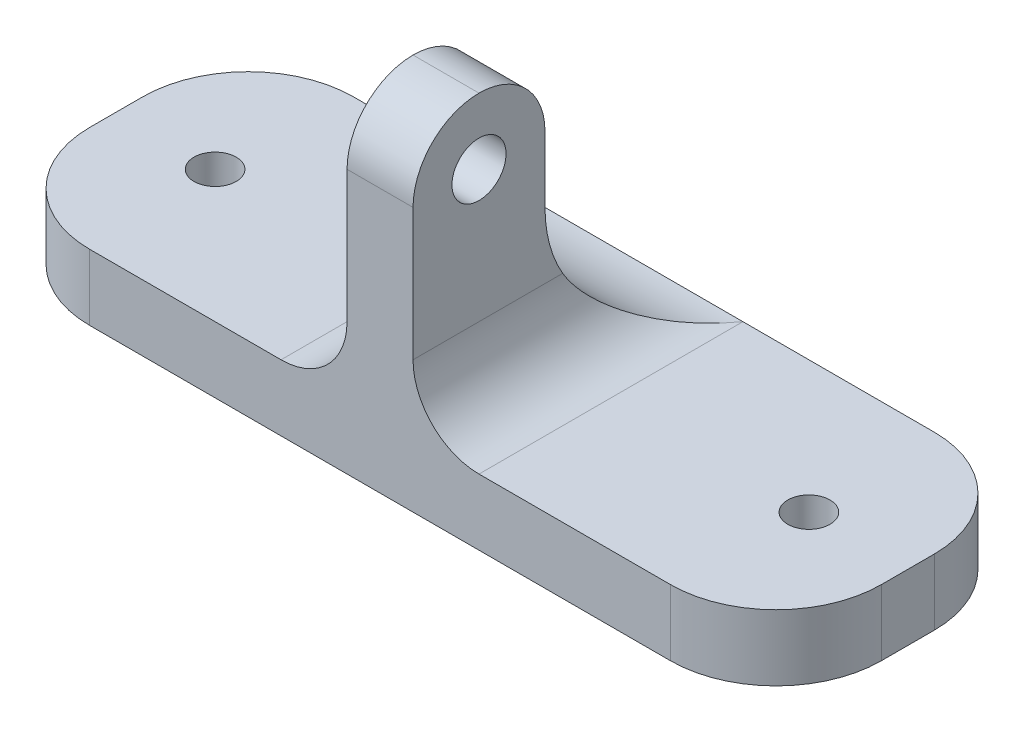
SolidWorks part; units mm, degrees
ref_plane "前视基准面" through (0, 0, 0) normal (0, 0, 1) x (1, 0, 0)
ref_plane "上视基准面" through (0, 0, 0) normal (0, 1, 0) x (1, 0, 0)
ref_plane "右视基准面" through (0, 0, 0) normal (1, 0, 0) x (0, 0, -1)
sketch "草图1" plane through (0, 0, 0) normal (0, 0, 1) x (1, 0, 0)
  line L1 (0, 0) -> (20, 0)
  line L2 (0, 0) -> (0, 15)
  line L3 (0, 15) -> (20, 15)
  line L4 (20, 0) -> (20, 15)
  dimension "D1" = 20
  dimension "D2" = 15
extrude "凸台-拉伸1" add sketch "草图1" along normal blind 10
sketch "草图2" plane through (0, 0, 0) normal (0, -1, 0) x (1, 0, 0)
  line L0 (20, 10) -> (20, 0) construction
  line L1 (-20, 10) -> (40, 10)
  line L2 (-20, 10) -> (-20, -10)
  line L3 (-20, -10) -> (40, -10)
  line L4 (40, 10) -> (40, -10)
  line L5 (0, 10) -> (20, 10) construction
  dimension "D1" = 60
  dimension "D2" = 20
  dimension "D3" = 20
  dimension "D4" = 0
extrude "凸台-拉伸2" add sketch "草图2" against normal blind 5
sketch "草图3" plane through (0, 0, 0) normal (0, -1, 0) x (1, 0, 0)
  line L0 (-20, 10) -> (40, 10) construction
  line L1 (-20, 10) -> (-20, -10) construction
  circle A0 centre (-12.5, 0) radius 1.6
  circle A1 centre (32.5, 0) radius 1.6
  dimension "D1" = 3.2
  dimension "D2" = 3.2
  dimension "D3" = 10
  dimension "D4" = 10
  dimension "D5" = 45
  dimension "D6" = 7.5
extrude "切除-拉伸1" cut sketch "草图3" against normal blind 21
fillet "圆角1" radius 8 4 edges at (-20, 2.5, -10) (-20, 2.5, 10) (40, 2.5, -10) (40, 2.5, 10)
sketch "草图4" plane through (0, 0, 10) normal (0, 0, 1) x (1, 0, 0)
  line L0 (-12, 0) -> (32, 0) construction
  line L1 (20, 5) -> (20, 15) construction
  circle A0 centre (10, 8) radius 2.1
  dimension "D1" = 4.2
  dimension "D2" = 8
  dimension "D3" = 10
extrude "切除-拉伸2" [suppressed] cut sketch "草图4" against normal blind 21
sketch "草图5" plane through (0, 0, 10) normal (0, 0, 1) x (1, 0, 0)
  line L0 (0, 5) -> (-12, 5) construction
  line L1 (-0.15, 5) -> (-10.15, 5)
  line L2 (-0.15, 5) -> (-0.15, 0)
  line L3 (-0.15, 0) -> (-10.15, 0)
  line L4 (-10.15, 5) -> (-10.15, 0)
  line L5 (-12, 0) -> (32, 0) construction
  line L6 (32, 5) -> (20, 5) construction
  line L7 (20.15, 5) -> (30.15, 5)
  line L8 (20.15, 5) -> (20.15, 0)
  line L9 (20.15, 0) -> (30.15, 0)
  line L10 (30.15, 5) -> (30.15, 0)
  line L11 (20, 5) -> (20, 15) construction
  line L12 (0, 15) -> (0, 5) construction
  dimension "D1" = 0.15
  dimension "D2" = 0.15
  dimension "D3" = 10
  dimension "D4" = 10
extrude "凸台-拉伸3" [suppressed] add sketch "草图5" along normal blind 5
chamfer "倒角1" [suppressed] distance 5 angle 45
sketch "草图6" plane through (0, 15, 0) normal (0, 1, 0) x (1, 0, 0)
  line L4 (20, 0) -> (0, 0)
  line L5 (0, 0) -> (0, -10)
  line L6 (0, -10) -> (20, -10)
  line L7 (20, -10) -> (20, 0)
  line L8 (20, 0) -> (0, 0)
  line L9 (0, 0) -> (0, -10)
  line L10 (0, -10) -> (20, -10)
  line L11 (20, -10) -> (20, 0)
  dimension "D1" = 0
extrude "切除-拉伸3" cut sketch "草图6" against normal blind 10
sketch "草图7" plane through (0, 5, 0) normal (0, 1, 0) x (1, 0, 0)
  line L0 (32, -10) -> (-12, -10) construction
  line L1 (7.5, -10) -> (12.5, -10)
  line L2 (7.5, -10) -> (7.5, 0)
  line L3 (7.5, 0) -> (12.5, 0)
  line L4 (12.5, -10) -> (12.5, 0)
  line L5 (40, 2) -> (40, -2) construction
  line L6 (-20, -2) -> (-20, 2) construction
  dimension "D1" = 5
  dimension "D2" = 27.5
  dimension "D3" = 27.5
  dimension "D4" = 10
extrude "凸台-拉伸4" add sketch "草图7" along normal blind 20
sketch "草图8" plane through (7.5, 0, 0) normal (-1, 0, 0) x (0, 0, 1)
  line L0 (0, 25) -> (10, 25) construction
  circle A0 centre (5, 20) radius 2.05
  dimension "D1" = 4.1
  dimension "D2" = 5
extrude "切除-拉伸4" cut sketch "草图8" against normal blind 20
fillet "圆角2" radius 5 2 edges at (10, 25, 0) (10, 25, 10)
fillet "圆角3" radius 10 1 edges at (10, 5, 0)
fillet "圆角4" radius 5 2 edges at (12.5, 5, 0) (7.5, 5, 0)
